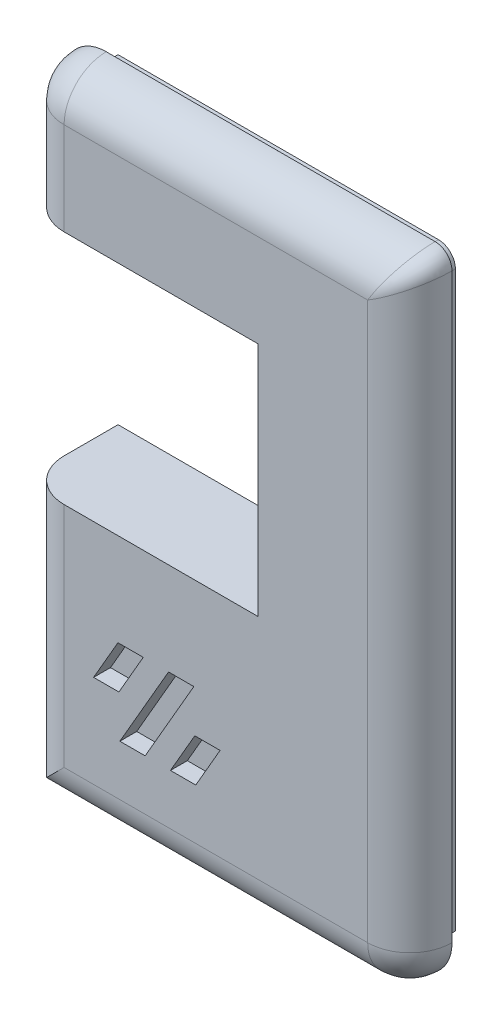
SolidWorks part; units mm, degrees
ref_plane "Front Plane" through (0, 0, 0) normal (0, 0, 1) x (1, 0, 0)
ref_plane "Top Plane" through (0, 0, 0) normal (0, 1, 0) x (1, 0, 0)
ref_plane "Right Plane" through (0, 0, 0) normal (1, 0, 0) x (0, 0, -1)
sketch "Sketch1" plane through (0, 0, 0) normal (0, 0, 1) x (1, 0, 0)
  line L1 (-14.899, 13.3838) -> (5.101, 13.3838)
  line L2 (-14.899, 13.3838) -> (-14.899, -21.6162)
  line L3 (-14.899, -21.6162) -> (5.101, -21.6162)
  line L4 (5.101, 13.3838) -> (5.101, -21.6162)
  dimension "D1" = 20
  dimension "D2" = 35
extrude "Boss-Extrude1" add sketch "Sketch1" along normal blind 3.2
fillet "Fillet1" radius 1 1 edges at (5.101, 13.3838, 1.6)
sketch "Sketch2" plane through (0, 0, 3.2) normal (0, 0, 1) x (1, 0, 0)
  line L0 (-14.899, 13.3838) -> (-14.899, -21.6162) construction
  line L1 (-14.899, -5.6162) -> (-0.899, -5.6162)
  line L2 (-14.899, -5.6162) -> (-14.899, 8.3838)
  line L3 (-14.899, 8.3838) -> (-0.899, 8.3838)
  line L4 (-0.899, -5.6162) -> (-0.899, 8.3838)
  line L5 (-14.899, -21.6162) -> (5.101, -21.6162) construction
  dimension "D1" = 16
  dimension "D2" = 14
  dimension "D3" = 14
extrude "Cut-Extrude1" cut sketch "Sketch2" against normal through all and the other way blind 12.5
sketch "Sketch4" plane through (0, 0, 3.2) normal (0, 0, 1) x (1, 0, 0)
  line L0 (4.101, 13.3838) -> (-14.899, 13.3838) construction
  line L1 (-14.899, 16.3838) -> (8.101, 16.3838)
  line L2 (-14.899, 16.3838) -> (-14.899, -21.6162)
  line L3 (-14.899, -21.6162) -> (8.101, -21.6162)
  line L4 (8.101, 16.3838) -> (8.101, -21.6162)
  line L5 (5.101, -21.6162) -> (5.101, 12.3838) construction
  dimension "D1" = 3
  dimension "D2" = 3
  dimension "D3" = 38
extrude "Boss-Extrude2" add sketch "Sketch4" along normal blind 2.5
fillet "Fillet2" radius 1 1 edges at (8.101, 16.3838, 4.45)
sketch "Sketch5" plane through (0, 0, 3.2) normal (0, 0, -1) x (-1, 0, 0)
  line L1 (0.899, 8.3838) -> (14.899, 8.3838)
  line L2 (0.899, 8.3838) -> (0.899, -5.6162)
  line L3 (0.899, -5.6162) -> (14.899, -5.6162)
  line L4 (14.899, 8.3838) -> (14.899, -5.6162)
extrude "Cut-Extrude2" cut sketch "Sketch5" against normal blind 2.5
fillet "Fillet3" radius 2.5 3 edges at (8.101, -3.1162, 5.7) (7.8081, 16.0909, 5.7) (-3.899, 16.3838, 5.7)
sketch "Sketch12" plane through (0, 0, 5.7) normal (0, 0, 1) x (1, 0, 0)
  line L0 (-9.2056, -11.1162) -> (-7.7056, -11.1162)
  line L1 (-7.7056, -11.1162) -> (-9.149, -13.6162)
  line L2 (-9.149, -13.6162) -> (-10.649, -13.6162)
  line L3 (-10.649, -13.6162) -> (-9.2056, -11.1162)
  line L4 (-6.2056, -11.1162) -> (-4.7056, -11.1162)
  line L5 (-4.7056, -11.1162) -> (-7.5924, -16.1162)
  line L6 (-7.5924, -16.1162) -> (-9.0924, -16.1162)
  line L7 (-9.0924, -16.1162) -> (-6.2056, -11.1162)
  line L8 (-6.0924, -16.1162) -> (-4.5924, -16.1162)
  line L9 (-4.5924, -16.1162) -> (-3.149, -13.6162)
  line L10 (-3.149, -13.6162) -> (-4.649, -13.6162)
  line L11 (-4.649, -13.6162) -> (-6.0924, -16.1162)
  line L13 (-0.899, -5.6162) -> (-14.899, -5.6162) construction
  line L14 (-14.899, -5.6162) -> (-14.899, -21.6162) construction
  dimension "D1" = 1.5
  dimension "D2" = 1.5
  dimension "D3" = 1.5
  dimension "D4" = 1.5
  dimension "D5" = 1.5
  dimension "D6" = 1.5
  dimension "D7" = 5
  dimension "D10" = 1.5
  dimension "D11" = 1.5
  dimension "D12" = 8
  dimension "D13" = 4.25
extrude "Cut-Extrude5" cut sketch "Sketch12" against normal blind 1
fillet "Fillet6" radius 2.5 4 edges at (7.3688, -21.6162, 4.9678) (-14.899, 15.6516, 4.9678) (-4.649, -21.6162, 5.7) (-14.899, -13.6162, 5.7)
sketch "Sketch13" plane through (0, 0, 0) normal (0, 0, -1) x (-1, 0, 0)
  line L0 (14.899, -5.6162) -> (14.899, -21.6162) construction
  line L1 (14.899, -21.6162) -> (-5.101, -21.6162) construction
  circle A0 centre (2.899, -13.6162) radius 3.1
  dimension "D1" = 6.2
  dimension "D2" = 12
  dimension "D3" = 8
extrude "Cut-Extrude6" cut sketch "Sketch13" against normal blind 3.1
fillet "Fillet7" radius 0.5 1 edges at (-5.999, -13.6162, 0)
sketch "Sketch14" plane through (0, 0, 0) normal (0, 0, -1) x (-1, 0, 0)
  line L0 (0.899, 8.3838) -> (14.899, 8.3838) construction
  line L1 (14.899, 13.3838) -> (14.899, 8.3838) construction
  circle A0 centre (7.149, 10.8838) radius 1
  dimension "D1" = 2
  dimension "D2" = 2.5
  dimension "D3" = 7.75
extrude "Boss-Extrude3" add sketch "Sketch14" along normal blind 2
fillet "Fillet8" radius 1 1 edges at (-8.149, 10.8838, -2)
